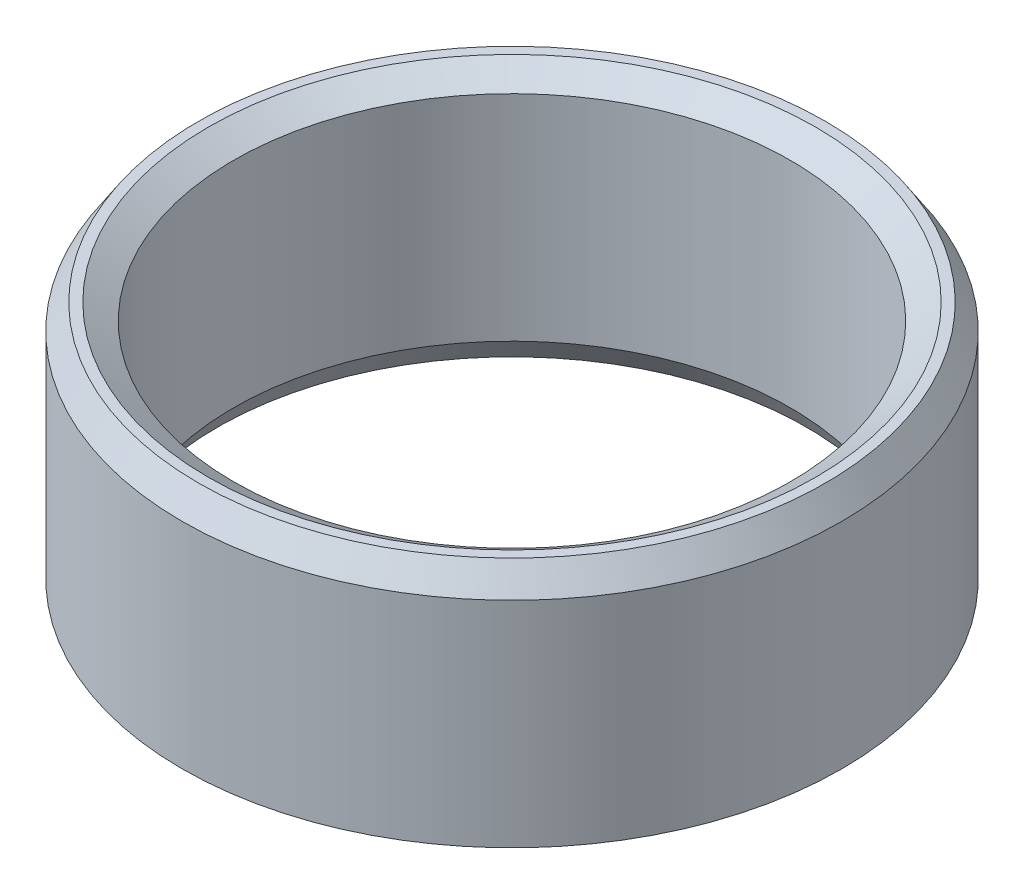
SolidWorks part; units mm, degrees
ref_plane "Front Plane" through (0, 0, 0) normal (0, 0, 1) x (1, 0, 0)
ref_plane "Top Plane" through (0, 0, 0) normal (0, 1, 0) x (1, 0, 0)
ref_plane "Right Plane" through (0, 0, 0) normal (1, 0, 0) x (0, 0, -1)
sketch "Sketch1" plane through (0, 0, 0) normal (0, 1, 0) x (1, 0, 0)
  circle A0 centre (0, 0) radius 22.5
  dimension "SLEEVE_OD" = 45
extrude "Boss-Extrude1" add sketch "Sketch1" along normal blind 17.4501
sketch "Sketch2" plane through (0, 0, 0) normal (0, 1, 0) x (1, 0, 0)
  circle A0 centre (0, 0) radius 19.0004
  dimension "BORE_D" = 38.0007
extrude "Cut-Extrude1" cut sketch "Sketch2" along normal through all
chamfer "Chamfer1" distance 1.7113 angle 33.005 4 edges at (0, 17.4501, 19.0004) (0, 0, 19.0004) (0, 0, 22.5) (0, 17.4501, 22.5) first distance on face at (0, 17.4501, 19.0004) first distance on face at (0, 0, 19.0004) first distance on face at (0, 17.4501, 22.5)
